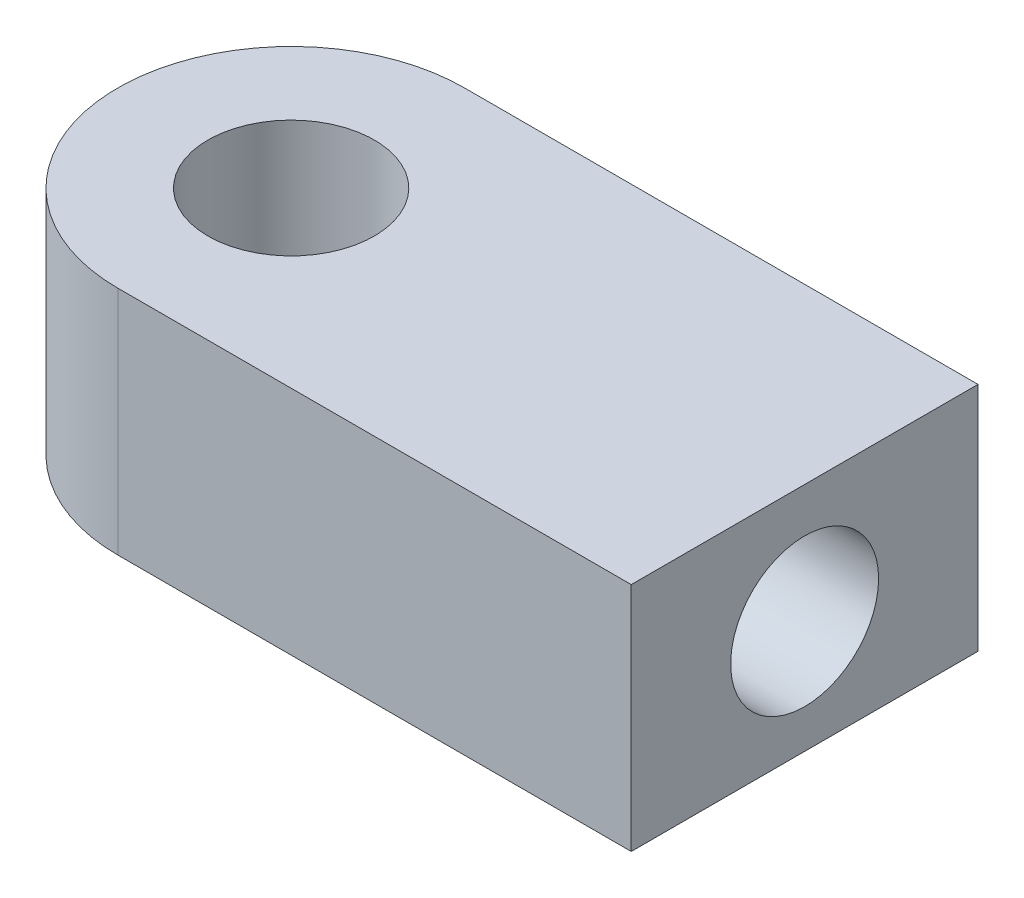
SolidWorks part; units mm, degrees
ref_plane "Front Plane" through (0, 0, 0) normal (0, 0, 1) x (1, 0, 0)
ref_plane "Top Plane" through (0, 0, 0) normal (0, 1, 0) x (1, 0, 0)
ref_plane "Right Plane" through (0, 0, 0) normal (1, 0, 0) x (0, 0, -1)
sketch "Sketch2" plane through (0, 0, 0) normal (0, 1, 0) x (1, 0, 0)
  line L0 (0, 4.7625) -> (14.1051, 4.7625)
  line L1 (14.1051, 4.7625) -> (14.1051, -4.7625)
  line L2 (14.1051, -4.7625) -> (0, -4.7625)
  arc A0 (0, 4.7625) -> (0, -4.7625) centre (0, 0) ccw
  circle A1 centre (0, 0) radius 2.286
  dimension "D1" = 4.572
  dimension "D2" = 4.7625
extrude "Boss-Extrude1" add sketch "Sketch2" along normal blind 6.35
sketch "Sketch3" plane through (14.1051, 0, 0) normal (1, 0, 0) x (0, 0, -1)
  circle A0 centre (0, 3.0961) radius 2.032
  dimension "D1" = 4.064
extrude "Cut-Extrude1" cut sketch "Sketch3" against normal blind 9.525
